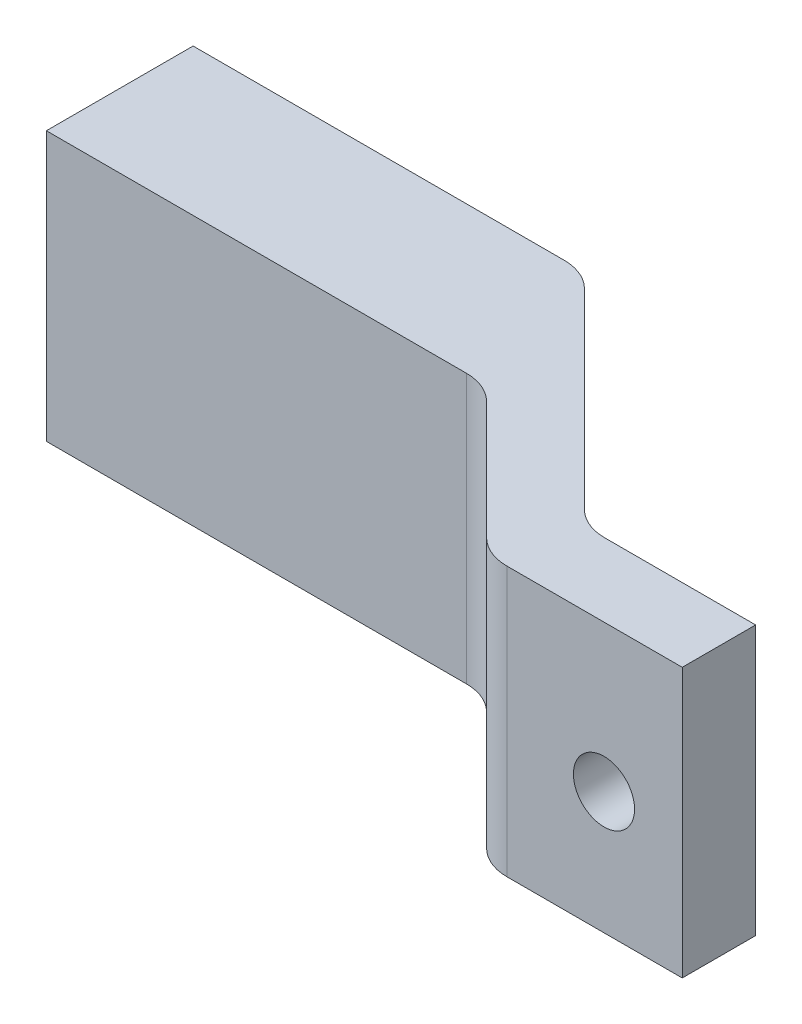
SolidWorks part; units mm, degrees
ref_plane "Alzado" through (0, 0, 0) normal (0, 0, 1) x (1, 0, 0)
ref_plane "Planta" through (0, 0, 0) normal (0, 1, 0) x (1, 0, 0)
ref_plane "Vista lateral" through (0, 0, 0) normal (1, 0, 0) x (0, 0, -1)
sketch "Croquis1" plane through (0, 0, 0) normal (0, 0, 1) x (1, 0, 0)
  line L1 (0, 0) -> (18, 0)
  line L2 (0, 0) -> (0, -11)
  line L3 (0, -11) -> (18, -11)
  line L4 (18, 0) -> (18, -11)
  dimension "D1" = 11
  dimension "D2" = 18
extrude "Saliente-Extruir1" add sketch "Croquis1" along normal blind 6
sketch "Croquis3" plane through (18, 0, 0) normal (1, 0, 0) x (0, 0, -1)
  line L1 (0, 0) -> (-12, 0)
  line L2 (0, 0) -> (0, -11.0025)
  line L3 (0, -11.0025) -> (-12, -11.0025)
  line L4 (-12, 0) -> (-12, -11.0025)
  dimension "D1" = 12
  dimension "D2" = 11.0025
extrude "Saliente-Extruir2" add sketch "Croquis3" along normal blind 8
sketch "Croquis4" plane through (26, 0, 0) normal (1, 0, 0) x (0, 0, -1)
  line L0 (-12, -11.0025) -> (0, -11.0025) construction
  line L1 (-12, 0) -> (-9, 0)
  line L2 (-12, 0) -> (-12, -11.0025)
  line L3 (-12, -11.0025) -> (-9, -11.0025)
  line L4 (-9, 0) -> (-9, -11.0025)
  dimension "D1" = 3
extrude "Saliente-Extruir3" add sketch "Croquis4" along normal blind 6
sketch "Croquis5" plane through (0, 0, 0) normal (-1, 0, 0) x (0, 0, 1)
  line L0 (0, 0) -> (0, -11) construction
  line L2 (6, -11) -> (0, -11) construction
  circle A0 centre (2.2, -5.7) radius 1.25
  dimension "D1" = 2.5
  dimension "D2" = 2.2
  dimension "D3" = 5.3
extrude "Cortar-Extruir1" cut sketch "Croquis5" against normal blind 10
sketch "Croquis6" plane through (0, 0, 12) normal (0, 0, 1) x (1, 0, 0)
  line L0 (32, 0) -> (32, -11.0025) construction
  line L1 (32, -11.0025) -> (18, -11.0025) construction
  circle A0 centre (28.8, -6.0025) radius 1.25
  dimension "D1" = 2.5
  dimension "D2" = 3.2
  dimension "D3" = 5
extrude "Cortar-Extruir2" cut sketch "Croquis6" against normal blind 10
chamfer "Chaflán1" distance 10 angle 45 1 edges at (26, -5.5012, 0)
chamfer "Chaflán2" distance 6 angle 45 1 edges at (18, -5.5012, 12)
fillet "Redondeo1" radius 2 4 edges at (16, -5.5, 0) (25, -5.5012, 9) (24, -5.5012, 12) (18, -5.5, 6)
